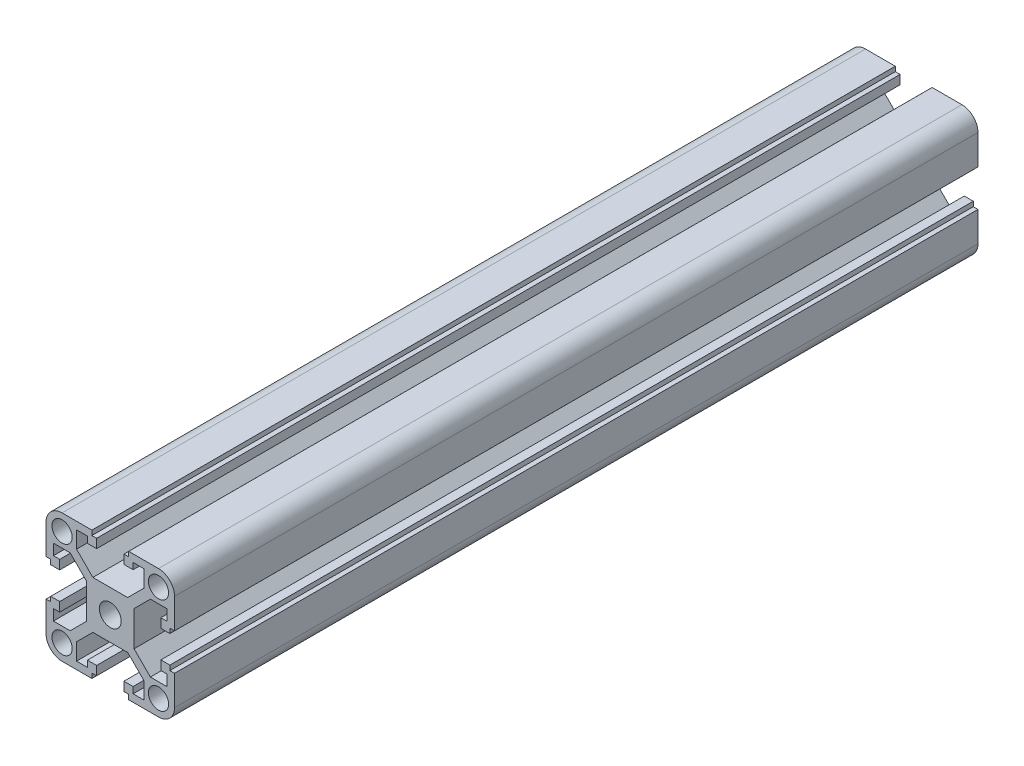
SolidWorks part; units mm, degrees
material "АД1 ГОСТ 4784-97"
ref_plane "Спереди" through (0, 0, 0) normal (0, 0, 1) x (1, 0, 0)
ref_plane "Сверху" through (0, 0, 0) normal (0, 1, 0) x (1, 0, 0)
ref_plane "Справа" through (0, 0, 0) normal (1, 0, 0) x (0, 0, -1)
ref_axis "ОсьX" through (-88.99, 0, 0) along (1, 0, 0)
ref_axis "ОсьZ" through (0, 55, 0) along (0, -1, 0)
ref_axis "ОсьY" through (0, 0, -88.99) along (0, 0, 1)
sketch "Эскиз1" plane through (0, 0, 0) normal (0, 0, 1) x (1, 0, 0)
  line L0 (-15, 20) -> (-5.7274, 20)
  line L1 (-5.7274, 20) -> (-5.7274, 18.5304)
  line L2 (-5.7274, 18.5304) -> (-4.25, 18.5304)
  line L3 (-4.25, 18.5304) -> (-4.25, 15.732)
  line L4 (-4.25, 15.732) -> (-7.1118, 15.732)
  line L5 (-7.1118, 15.732) -> (-7.1118, 17.7)
  line L6 (-7.1118, 17.7) -> (-10.5, 17.7)
  line L7 (-10.5, 17.7) -> (-10.5, 12.4799)
  line L8 (-10.5, 12.4799) -> (-5.4201, 7.4)
  line L9 (-20, 15) -> (-20, 5.7274)
  line L10 (0, 0) -> (0, 8.4096) construction
  line L11 (-15, 15) -> (0, 0) construction
  line L12 (10.5, 12.4799) -> (5.4201, 7.4)
  line L13 (10.5, 17.7) -> (10.5, 12.4799)
  line L14 (7.1118, 17.7) -> (10.5, 17.7)
  line L15 (7.1118, 15.732) -> (7.1118, 17.7)
  line L16 (4.25, 15.732) -> (7.1118, 15.732)
  line L17 (4.25, 18.5304) -> (4.25, 15.732)
  line L18 (5.7274, 18.5304) -> (4.25, 18.5304)
  line L19 (5.7274, 20) -> (5.7274, 18.5304)
  line L20 (15, 20) -> (5.7274, 20)
  line L21 (-5.4201, 7.4) -> (5.4201, 7.4)
  line L22 (-8.8445, 0) -> (0, 0) construction
  line L23 (-12.4799, 10.5) -> (-7.4, 5.4201)
  line L24 (-17.7, 10.5) -> (-12.4799, 10.5)
  line L25 (-17.7, 7.1118) -> (-17.7, 10.5)
  line L26 (-15.732, 7.1118) -> (-17.7, 7.1118)
  line L27 (-15.732, 4.25) -> (-15.732, 7.1118)
  line L28 (-18.5304, 4.25) -> (-15.732, 4.25)
  line L29 (-18.5304, 5.7274) -> (-18.5304, 4.25)
  line L30 (-20, 5.7274) -> (-18.5304, 5.7274)
  line L31 (18.5304, 5.7274) -> (18.5304, 4.25)
  line L32 (18.5304, 4.25) -> (15.732, 4.25)
  line L33 (15.732, 4.25) -> (15.732, 7.1118)
  line L34 (15.732, 7.1118) -> (17.7, 7.1118)
  line L35 (12.4799, 10.5) -> (7.4, 5.4201)
  line L36 (17.7, 10.5) -> (12.4799, 10.5)
  line L37 (17.7, 7.1118) -> (17.7, 10.5)
  line L38 (20, 5.7274) -> (18.5304, 5.7274)
  line L39 (20, 15) -> (20, 5.7274)
  line L40 (20, -15) -> (20, -5.7274)
  line L41 (20, -5.7274) -> (18.5304, -5.7274)
  line L42 (17.7, -7.1118) -> (17.7, -10.5)
  line L43 (17.7, -10.5) -> (12.4799, -10.5)
  line L44 (12.4799, -10.5) -> (7.4, -5.4201)
  line L45 (15.732, -7.1118) -> (17.7, -7.1118)
  line L46 (15.732, -4.25) -> (15.732, -7.1118)
  line L47 (18.5304, -4.25) -> (15.732, -4.25)
  line L48 (18.5304, -5.7274) -> (18.5304, -4.25)
  line L49 (-20, -5.7274) -> (-18.5304, -5.7274)
  line L50 (-18.5304, -5.7274) -> (-18.5304, -4.25)
  line L51 (-18.5304, -4.25) -> (-15.732, -4.25)
  line L52 (-15.732, -4.25) -> (-15.732, -7.1118)
  line L53 (-15.732, -7.1118) -> (-17.7, -7.1118)
  line L54 (-17.7, -7.1118) -> (-17.7, -10.5)
  line L55 (-17.7, -10.5) -> (-12.4799, -10.5)
  line L56 (-12.4799, -10.5) -> (-7.4, -5.4201)
  line L57 (-5.4201, -7.4) -> (5.4201, -7.4)
  line L58 (15, -20) -> (5.7274, -20)
  line L59 (5.7274, -20) -> (5.7274, -18.5304)
  line L60 (5.7274, -18.5304) -> (4.25, -18.5304)
  line L61 (4.25, -18.5304) -> (4.25, -15.732)
  line L62 (4.25, -15.732) -> (7.1118, -15.732)
  line L63 (7.1118, -15.732) -> (7.1118, -17.7)
  line L64 (7.1118, -17.7) -> (10.5, -17.7)
  line L65 (10.5, -17.7) -> (10.5, -12.4799)
  line L66 (10.5, -12.4799) -> (5.4201, -7.4)
  line L67 (-20, -15) -> (-20, -5.7274)
  line L68 (-10.5, -12.4799) -> (-5.4201, -7.4)
  line L69 (-10.5, -17.7) -> (-10.5, -12.4799)
  line L70 (-7.1118, -17.7) -> (-10.5, -17.7)
  line L71 (-7.1118, -15.732) -> (-7.1118, -17.7)
  line L72 (-4.25, -15.732) -> (-7.1118, -15.732)
  line L73 (-4.25, -18.5304) -> (-4.25, -15.732)
  line L74 (-5.7274, -18.5304) -> (-4.25, -18.5304)
  line L75 (-5.7274, -20) -> (-5.7274, -18.5304)
  line L76 (-15, -20) -> (-5.7274, -20)
  line L77 (-7.4, 5.4201) -> (-7.4, -5.4201)
  line L78 (7.4, 5.4201) -> (7.4, -5.4201)
  circle A0 centre (0, 0) radius 3.4
  circle A1 centre (-15, 15) radius 3.15
  arc A2 (-15, 20) -> (-20, 15) centre (-15, 15) ccw
  arc A3 (15, 20) -> (20, 15) centre (15, 15) cw
  circle A4 centre (15, 15) radius 3.15
  circle A5 centre (15, -15) radius 3.15
  arc A6 (15, -20) -> (20, -15) centre (15, -15) ccw
  arc A7 (-15, -20) -> (-20, -15) centre (-15, -15) cw
  circle A8 centre (-15, -15) radius 3.15
  dimension "D1" = 6.8
  dimension "D2" = 6.3
  dimension "D3" = 40
  dimension "D8" = 30
  dimension "D4" = 2.3
  dimension "D5" = 1.35
  dimension "D6" = 21
  dimension "D7" = 8.5
  dimension "D9" = 45
  dimension "D10" = 2.8
  dimension "D11" = 4
  dimension "D13" = 40
extrude "Бобышка-Вытянуть1" add sketch "Эскиз1" along normal mid plane 250
